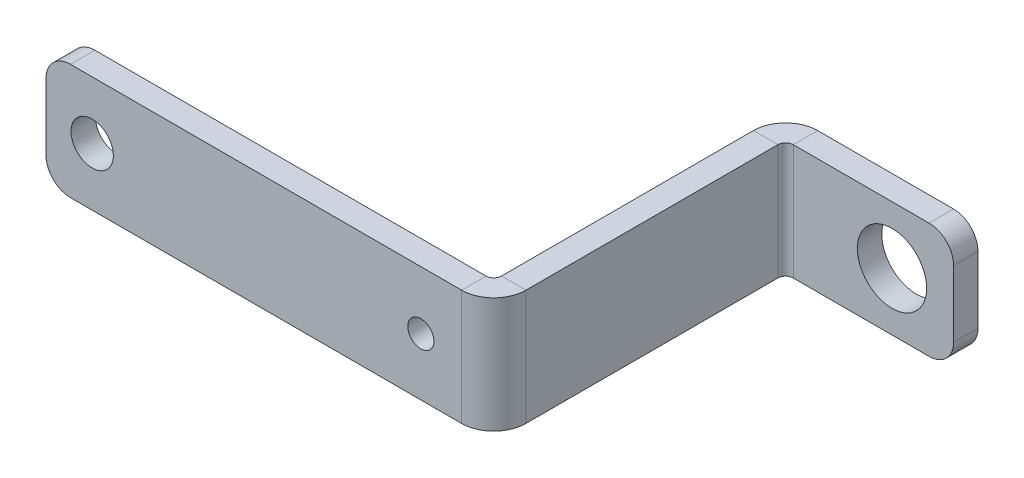
SolidWorks part; units mm, degrees
note: The reader was unsure of these and kept them because the rebuilt part matched: flange length of "Edge-Flange1", "Edge-Flange2".
material "3003-H14"
ref_plane "X-Y Datum" through (0, 0, 0) normal (0, 0, 1) x (1, 0, 0)
ref_plane "X-Z Datum" through (0, 0, 0) normal (0, 1, 0) x (1, 0, 0)
ref_plane "Y-Z Datum" through (0, 0, 0) normal (1, 0, 0) x (0, 0, -1)
sketch "Sketch2" plane through (0, 0, 0) normal (0, 0, 1) x (1, 0, 0)
  line L0 (79.9093, 321.1281) -> (79.9093, 306.1281) construction
  line L1 (79.9093, 306.1281) -> (73.9093, 306.1281)
  line L2 (73.9093, 306.1281) -> (73.9093, 321.1281)
  line L3 (73.9093, 321.1281) -> (79.9093, 321.1281)
  line L4 (79.9093, 306.1281) -> (127.9093, 306.1281)
  line L5 (127.9093, 306.1281) -> (127.9093, 321.1281)
  line L6 (127.9093, 321.1281) -> (79.9093, 321.1281)
  point P0 (79.9093, 313.6281)
  point P5 (79.9093, 313.6281)
  dimension "D1" = 15
  dimension "D2" = 6
  dimension "D3" = 48
base flange "Base-Flange1" sketch "Sketch2" thickness 3.175 reverse thickness direction yes parameters "D1"=10
edge flange "Edge-Flange1" sketch "Sketch7" flange angle 90 flange length 36.913 flange position bend outside bend radius 1 thickness 3.175 relief rectangular parameters "D6"=0
sketch "Sketch7" plane through (127.9093, 0, 0) normal (1, 0, 0) x (0, -1, 0)
  line L0 (-306.1281, 0) -> (-321.1281, 0) construction
  line L1 (-306.1281, 0) -> (-321.1281, 0)
  line L2 (-321.1281, 0) -> (-321.1281, 33.738)
  line L3 (-321.1281, 33.738) -> (-306.1281, 33.738)
  line L4 (-306.1281, 33.738) -> (-306.1281, 0)
bend "EdgeBend1" bend radius 1 bend angle 90 parameters "D5"=1
edge flange "Edge-Flange2" sketch "Sketch10" flange angle 90 flange length 25 flange position bend outside bend radius 1 thickness 3.175 relief rectangular parameters "D6"=0
sketch "Sketch10" plane through (132.0843, 0, -33.738) normal (0, 0, -1) x (0, 1, 0)
  line L2 (306.1281, 0) -> (306.1281, 21.825)
  line L3 (306.1281, 21.825) -> (321.1281, 21.825)
  line L4 (321.1281, 21.825) -> (321.1281, 0)
  line L7 (306.1281, 0) -> (321.1281, 0) construction
  line L8 (306.1281, 0) -> (321.1281, 0)
bend "EdgeBend2" bend radius 1 bend angle 90 parameters "D5"=2
hole_wizard "M5 Clearance Hole1" positions "Sketch14" profile "Sketch13" hole size "M5" standard "ANSI Metric" end condition through all
sketch "Sketch14" plane through (0, 0, 3.175) normal (0, 0, 1) x (1, 0, 0)
  point P0 (79.9093, 313.6281)
sketch "Sketch13" plane through (79.9093, 313.6281, 3.175) normal (1, 0, 0) x (0, -1, 0)
  line L0 (0, 0) -> (0, 41.088)
  line L1 (0, 41.088) -> (2.75, 41.088)
  line L2 (2.75, 41.088) -> (2.75, 0)
  line L5 (2.75, 0) -> (0, 0)
  line L11 (0, -6.35) -> (0, 107.95) construction
  dimension "Thru Hole Dia." = 5.5
  dimension "Thru Hole Depth" = 41.088
sketch "Sketch15" plane through (0, 0, -34.738) normal (0, 0, 1) x (1, 0, 0)
  line L0 (145.9093, 306.1281) -> (145.9093, 321.1281) construction
  line L1 (153.9093, 306.1281) -> (133.0843, 306.1281) construction
  line L2 (133.0843, 321.1281) -> (153.9093, 321.1281) construction
  line L3 (153.9093, 321.1281) -> (153.9093, 306.1281) construction
  point P6 (145.9093, 313.6281)
  dimension "D1" = 8
hole_wizard "M8 Clearance Hole1" positions "Sketch15" profile "Sketch16" hole size "M8" standard "ANSI Metric" end condition through all
sketch "Sketch16" plane through (145.9093, 313.6281, -34.738) normal (1, 0, 0) x (0, -1, 0)
  line L0 (0, 0) -> (0, 3.175)
  line L1 (0, 3.175) -> (4.5, 3.175)
  line L2 (4.5, 3.175) -> (4.5, 0)
  line L5 (4.5, 0) -> (0, 0)
  line L11 (0, -6.35) -> (0, 107.95) construction
  dimension "Thru Hole Dia." = 9
  dimension "Thru Hole Depth" = 3.175
fillet "Fillet1" radius 3.175 4 edges at (153.9093, 321.1281, -36.3255) (153.9093, 306.1281, -36.3255) (73.9093, 321.1281, 1.5875) (73.9093, 306.1281, 1.5875)
sketch "Sketch17" plane through (0, 0, 3.175) normal (0, 0, 1) x (1, 0, 0)
  point P9 (122.6093, 313.5781)
hole_wizard "M3 Clearance Hole1" positions "Sketch17" profile "Sketch18" hole size "M3" standard "ANSI Metric" end condition through all
sketch "Sketch18" plane through (122.6093, 313.5781, 3.175) normal (1, 0, 0) x (0, -1, 0)
  line L0 (0, 0) -> (0, 41.088)
  line L1 (0, 41.088) -> (1.7, 41.088)
  line L2 (1.7, 41.088) -> (1.7, 0)
  line L5 (1.7, 0) -> (0, 0)
  line L11 (0, -6.35) -> (0, 107.95) construction
  dimension "Thru Hole Dia." = 3.4
  dimension "Thru Hole Depth" = 41.088
sketch "Bend-Lines1" [suppressed] plane through (0, 0, 0) normal (0, 1, 0) x (1, 0, 0)
sketch "Bounding-Box1" [suppressed] plane through (0, 0, 0) normal (0, 1, 0) x (1, 0, 0)
sheet metal parameters "Sheet-Metal8" thickness 3.175 parameters "D1"=10
flat pattern "Flat-Pattern8" [suppressed]
sketch "Bend-Lines2" plane through (0, 0, 0) normal (0, 1, 0) x (1, 0, 0)
sketch3d "Bounding-Box2" [suppressed]
  line L0 (73.9093, 306.1281, 0) -> (124.9093, 306.1281, 0) construction
  line L1 (73.9093, 321.1281, 0) -> (124.9093, 321.1281, 0) construction
  line L2 (73.9093, 306.1281, 0) -> (73.9093, 321.1281, 0) construction
  line L3 (124.9093, 306.1281, 0) -> (124.9093, 321.1281, 0) construction
sheet metal parameters "Sheet-Metal9" thickness 3.175 parameters "D1"=10
flat pattern "Flat-Pattern8"
sketch "Bend-Lines2" plane through (0, 0, 0) normal (0, 0, -1) x (-1, 0, 0)
  line L0 (-126.9415, 321.1281) -> (-126.9415, 306.1281) construction
  line L1 (-126.9415, 321.1281) -> (-126.9415, 306.1281) construction
sketch3d "Bounding-Box2" [suppressed]
  line L0 (-73.9093, 306.1281, 0) -> (-158.1487, 306.1281, 0) construction
  line L1 (-73.9093, 321.1281, 0) -> (-158.1487, 321.1281, 0) construction
  line L2 (-73.9093, 306.1281, 0) -> (-73.9093, 321.1281, 0) construction
  line L3 (-158.1487, 306.1281, 0) -> (-158.1487, 321.1281, 0) construction
bend of the flat pattern "Flatten-<EdgeBend1>1"
sheet metal parameters "Sheet-Metal10" thickness 3.175 parameters "D1"=10
flat pattern "Flat-Pattern8"
sketch "Bend-Lines2" plane through (0, 0, 0) normal (0, 0, -1) x (-1, 0, 0)
  line L0 (-126.9415, 321.1281) -> (-126.9415, 306.1281) construction
  line L1 (-126.9415, 321.1281) -> (-126.9415, 306.1281) construction
  line L2 (-160.1809, 321.1281) -> (-160.1809, 306.1281) construction
  line L3 (-160.1809, 321.1281) -> (-160.1809, 306.1281) construction
sketch3d "Bounding-Box2" [suppressed]
  line L0 (-73.9093, 306.1281, 0) -> (-176.0382, 306.1281, 0) construction
  line L1 (-73.9093, 321.1281, 0) -> (-176.0382, 321.1281, 0) construction
  line L2 (-73.9093, 306.1281, 0) -> (-73.9093, 321.1281, 0) construction
  line L3 (-176.0382, 306.1281, 0) -> (-176.0382, 321.1281, 0) construction
bend of the flat pattern "Flatten-<EdgeBend1>1"
bend of the flat pattern "Flatten-<EdgeBend2>1"
sheet metal parameters "Sheet-Metal11" thickness 3.175 parameters "D1"=10
flat pattern "Flat-Pattern8"
sketch "Bend-Lines2" plane through (0, 0, 0) normal (0, 0, -1) x (-1, 0, 0)
  line L0 (-126.9415, 321.1281) -> (-126.9415, 306.1281) construction
  line L1 (-126.9415, 321.1281) -> (-126.9415, 306.1281) construction
  line L2 (-163.7439, 321.1281) -> (-163.7439, 306.1281) construction
  line L3 (-163.7439, 321.1281) -> (-163.7439, 306.1281) construction
sketch3d "Bounding-Box2" [suppressed]
  line L0 (-73.9093, 306.1281, 0) -> (-186.6012, 306.1281, 0) construction
  line L1 (-73.9093, 321.1281, 0) -> (-186.6012, 321.1281, 0) construction
  line L2 (-73.9093, 306.1281, 0) -> (-73.9093, 321.1281, 0) construction
  line L3 (-186.6012, 306.1281, 0) -> (-186.6012, 321.1281, 0) construction
bend of the flat pattern "Flatten-<EdgeBend1>1"
bend of the flat pattern "Flatten-<EdgeBend2>1"
sheet metal parameters "Sheet-Metal12" thickness 3.175 parameters "D1"=10
flat pattern "Flat-Pattern8"
sketch "Bend-Lines2" plane through (0, 0, 0) normal (0, 0, -1) x (-1, 0, 0)
  line L0 (-126.9415, 321.1281) -> (-126.9415, 306.1281) construction
  line L1 (-126.9415, 321.1281) -> (-126.9415, 306.1281) construction
  line L2 (-163.7439, 321.1281) -> (-163.7439, 306.1281) construction
  line L3 (-163.7439, 321.1281) -> (-163.7439, 306.1281) construction
sketch3d "Bounding-Box2" [suppressed]
  line L0 (-73.9093, 306.1281, 0) -> (-186.6012, 306.1281, 0) construction
  line L1 (-73.9093, 321.1281, 0) -> (-186.6012, 321.1281, 0) construction
  line L2 (-73.9093, 306.1281, 0) -> (-73.9093, 321.1281, 0) construction
  line L3 (-186.6012, 306.1281, 0) -> (-186.6012, 321.1281, 0) construction
bend of the flat pattern "Flatten-<EdgeBend1>1"
bend of the flat pattern "Flatten-<EdgeBend2>1"
sheet metal parameters "Sheet-Metal13" thickness 3.175 parameters "D1"=10
flat pattern "Flat-Pattern8"
sketch "Bend-Lines2" plane through (0, 0, 0) normal (0, 0, -1) x (-1, 0, 0)
  line L0 (-129.9415, 321.1281) -> (-129.9415, 306.1281) construction
  line L1 (-129.9415, 321.1281) -> (-129.9415, 306.1281) construction
  line L2 (-166.7439, 321.1281) -> (-166.7439, 306.1281) construction
  line L3 (-166.7439, 321.1281) -> (-166.7439, 306.1281) construction
sketch3d "Bounding-Box2" [suppressed]
  line L0 (-73.9093, 306.1281, 0) -> (-189.6012, 306.1281, 0) construction
  line L1 (-73.9093, 321.1281, 0) -> (-189.6012, 321.1281, 0) construction
  line L2 (-73.9093, 306.1281, 0) -> (-73.9093, 321.1281, 0) construction
  line L3 (-189.6012, 306.1281, 0) -> (-189.6012, 321.1281, 0) construction
bend of the flat pattern "Flatten-<EdgeBend1>1"
bend of the flat pattern "Flatten-<EdgeBend2>1"
